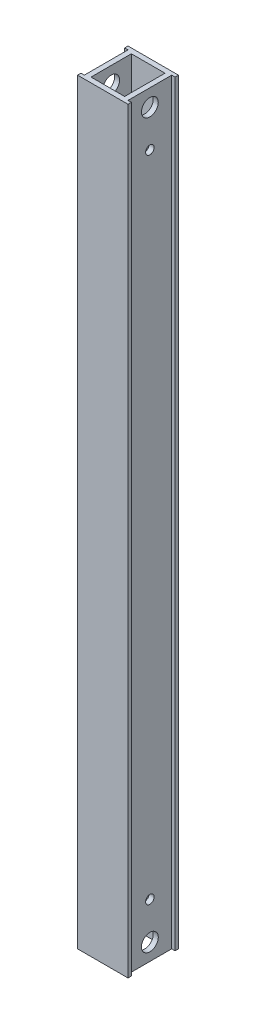
SolidWorks part; units mm, degrees
ref_plane "前视基准面" through (0, 0, 0) normal (0, 0, 1) x (1, 0, 0)
ref_plane "上视基准面" through (0, 0, 0) normal (0, 1, 0) x (1, 0, 0)
ref_plane "右视基准面" through (0, 0, 0) normal (1, 0, 0) x (0, 0, -1)
other "Configuration Table"
sketch "草图1" plane through (0, 0, 0) normal (0, 0, 1) x (1, 0, 0)
  line L0 (0, 0) -> (324.4923, 0) construction
  line L1 (0, 0) -> (0, 279.3401) construction
  line L2 (-15, 225) -> (15, 225)
  line L3 (-15, 225) -> (-15, -225)
  line L4 (-15, -225) -> (15, -225)
  line L5 (15, -225) -> (15, 225)
  point P6 (0, 225)
  point P10 (-15, 0)
  dimension "D1" = 450
  dimension "D2" = 30
extrude "凸台-拉伸1" add sketch "草图1" along normal blind 30
sketch "草图2" plane through (0, 225, 0) normal (0, 1, 0) x (1, 0, 0)
  line L0 (0, 0) -> (0, -20.1827) construction
  line L1 (0, -10) -> (15.4868, -10) construction
  line L2 (-15, -2) -> (-13, -2)
  line L3 (-13, -2) -> (-13, -28)
  line L4 (-13, -28) -> (-15, -28)
  line L5 (15, -30) -> (15, 0) construction
  line L6 (-15, -30) -> (-15, 0) construction
  line L7 (15, -28) -> (15, -2)
  line L8 (-15, -28) -> (-15, -2)
  line L9 (15, 0) -> (-15, 0) construction
  line L10 (15, -30) -> (-15, -30) construction
  line L11 (13, -28) -> (15, -28)
  line L12 (13, -2) -> (13, -28)
  line L13 (15, -2) -> (13, -2)
  dimension "D2" = 2
  dimension "D1" = 2
  dimension "D3" = 2
extrude "切除-拉伸1" cut sketch "草图2" against normal through all
shell "抽壳1" thickness 3 removed face at (0, -225, 15) removed face at (0, 225, 15)
sketch "草图3" plane through (13, 0, 0) normal (1, 0, 0) x (0, 0, -1)
  line L0 (0, 0) -> (170.4874, 0) construction
  line L1 (-15, 225) -> (-15, -46.9872) construction
  line L2 (-20, 205) -> (-10, 205)
  line L3 (-2, 225) -> (-28, 225) construction
  line L4 (-20, -195) -> (-10, -195)
  line L5 (-2, -225) -> (-28, -225) construction
  arc A1 (-10, 205) -> (-20, 205) centre (-15, 205) ccw
  arc A2 (-10, -195) -> (-20, -195) centre (-15, -195) cw
  point P18 (-15, -225)
  dimension "D1" = 20
  dimension "D2" = 5
  dimension "D3" = 30
  dimension "D4" = 5
sketch "草图5" plane through (13, 0, 0) normal (1, 0, 0) x (0, 0, -1)
  line L0 (-28, 215) -> (-2, 215) construction
  line L1 (-28, -225) -> (-28, 225) construction
  line L2 (-2, -225) -> (-2, 225) construction
  line L3 (-20, 205) -> (-10, 205) construction
  line L4 (-28, 0) -> (-2, 0) construction
  line L5 (-28, -225) -> (-28, 225) construction
  circle A0 centre (-15, 215) radius 5
  circle A1 centre (-15, -215) radius 5
  dimension "D1" = 10
extrude "切除-拉伸2" cut sketch "草图5" against normal blind 30 contours A0 | A1
sketch "草图6" plane through (13, 0, 0) normal (1, 0, 0) x (0, 0, -1)
  line L0 (-28, 193) -> (-2, 193) construction
  line L1 (-28, -225) -> (-28, 225) construction
  line L2 (-2, -225) -> (-2, 225) construction
  line L3 (-20, 205) -> (-10, 205) construction
  circle A0 centre (-15, 193) radius 2.55
  dimension "D1" = 12
extrude "切除-拉伸3" cut sketch "草图6" against normal blind 5 contours A0
ref_plane "基准面1" through (0, 0, 0) normal (0, 1, 0) x (1, 0, 0)
mirror "镜向1" about plane through (0, 0, 0) normal (0, 1, 0) of "切除-拉伸3"
